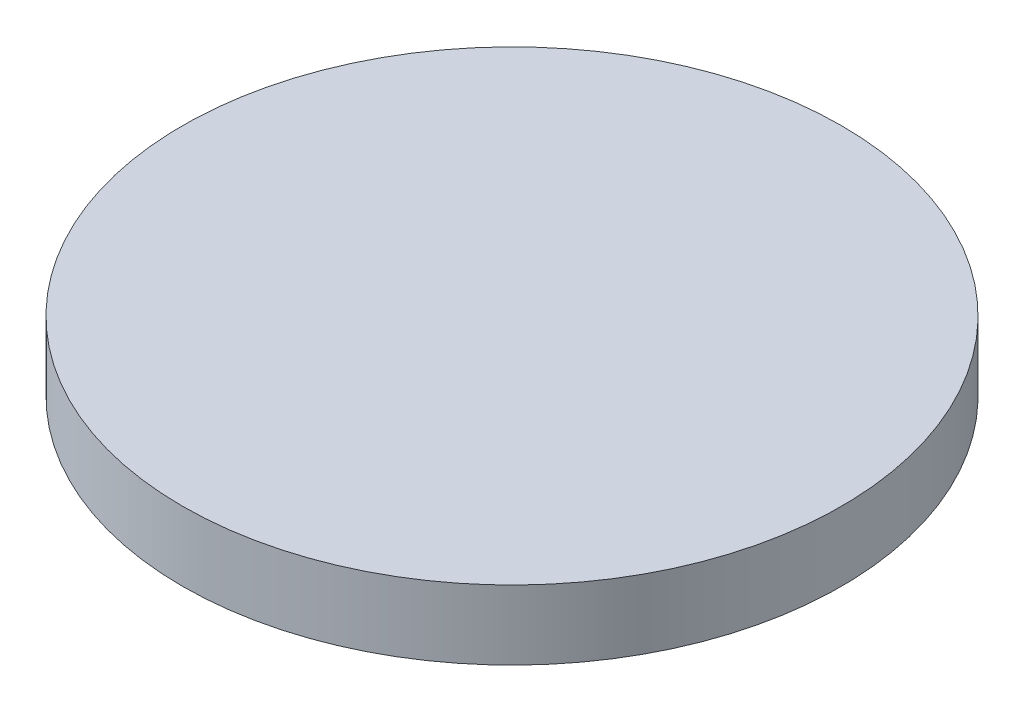
SolidWorks part; units mm, degrees
material "Сосна"
ref_plane "Спереди" through (0, 0, 0) normal (0, 0, 1) x (1, 0, 0)
ref_plane "Сверху" through (0, 0, 0) normal (0, 1, 0) x (1, 0, 0)
ref_plane "Справа" through (0, 0, 0) normal (1, 0, 0) x (0, 0, -1)
sketch "Эскиз1" plane through (0, 0, 0) normal (0, 1, 0) x (1, 0, 0)
  circle A0 centre (0, 0) radius 19
extrude "Бобышка-Вытянуть1" add sketch "Эскиз1" along normal blind 4
